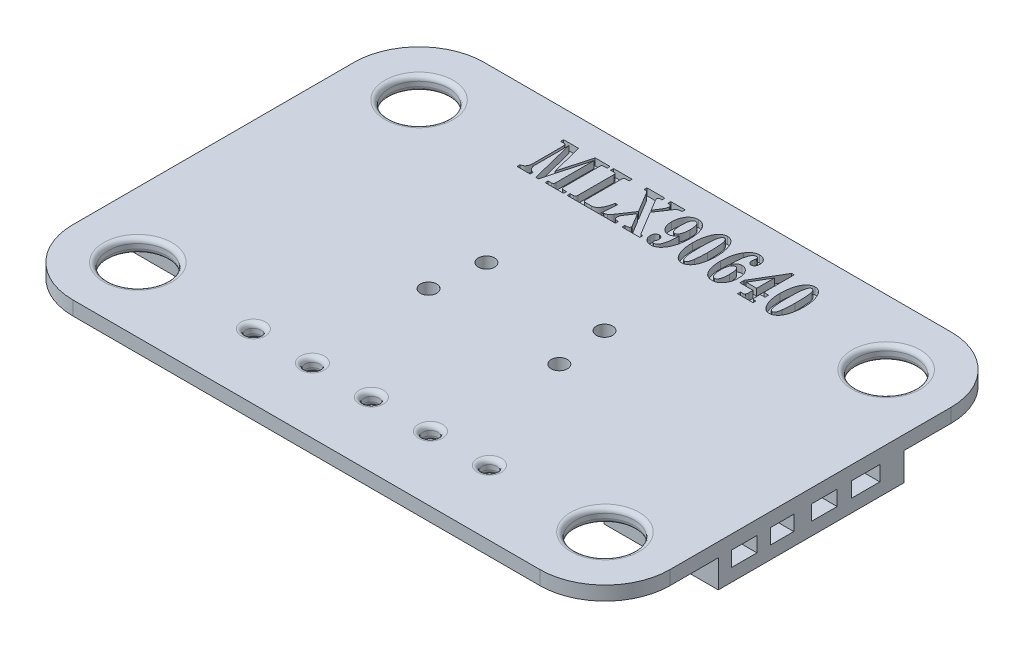
SolidWorks part; units mm, degrees
ref_plane "Alzado" through (0, 0, 0) normal (0, 0, 1) x (1, 0, 0)
ref_plane "Planta" through (0, 0, 0) normal (0, 1, 0) x (1, 0, 0)
ref_plane "Vista lateral" through (0, 0, 0) normal (1, 0, 0) x (0, 0, -1)
sketch "Croquis2" plane through (0, 0, 0) normal (0, 1, 0) x (1, 0, 0)
  line L1 (-10.05, 8.85) -> (10.05, 8.85)
  line L2 (-12.85, 6.05) -> (-12.85, -6.05)
  line L3 (-10.05, -8.85) -> (10.05, -8.85)
  line L4 (12.85, 6.05) -> (12.85, -6.05)
  line L5 (-12.85, 8.85) -> (12.85, -8.85) construction
  line L6 (-12.85, -8.85) -> (12.85, 8.85) construction
  arc A0 (10.05, -8.85) -> (12.85, -6.05) centre (10.05, -6.05) ccw
  arc A1 (-12.85, -6.05) -> (-10.05, -8.85) centre (-10.05, -6.05) ccw
  arc A2 (10.05, 8.85) -> (12.85, 6.05) centre (10.05, 6.05) cw
  arc A3 (-10.05, 8.85) -> (-12.85, 6.05) centre (-10.05, 6.05) ccw
  point P0 (0, 0)
  dimension "D3" = 2.8
  dimension "D1" = 17.7
  dimension "D2" = 25.7
extrude "Saliente-Extruir1" add sketch "Croquis2" along normal blind 0.6
sketch "Croquis3" plane through (0, 0.6, 0) normal (0, 1, 0) x (1, 0, 0)
  line L0 (-10.05, -6.05) -> (-5.08, -6.05) construction
  line L1 (-5.08, -6.05) -> (-2.54, -6.05) construction
  line L2 (-2.54, -6.05) -> (0, -6.05) construction
  line L3 (0, -6.05) -> (2.54, -6.05) construction
  line L4 (5.08, -6.05) -> (10.05, -6.05) construction
  line L5 (2.19, 1.4404) -> (-2.19, 1.4404) construction
  line L6 (2.54, -6.05) -> (5.08, -6.05) construction
  line L7 (2.2166, 1.3065) -> (-2.8146, -0.7775) construction
  line L8 (-3.1379, -0.9115) -> (-6.0577, -2.1209) construction
  circle A0 centre (-10.05, 6.05) radius 1.27
  circle A1 centre (10.05, 6.05) radius 1.27
  circle A2 centre (10.05, -6.05) radius 1.27
  circle A3 centre (-10.05, -6.05) radius 1.27
  circle A4 centre (-5.08, -6.05) radius 0.32
  circle A5 centre (-2.54, -6.05) radius 0.32
  circle A6 centre (0, -6.05) radius 0.32
  circle A7 centre (2.54, -6.05) radius 0.32
  circle A8 centre (5.08, -6.05) radius 0.32
  arc A9 (-2.6941, 1.1262) -> (-2.8874, -0.4352) centre (0, 0) ccw
  circle A10 centre (-2.54, 1.4404) radius 0.35
  circle A12 centre (2.54, 1.4404) radius 0.35
  circle A14 centre (-2.8146, -0.7775) radius 0.35
  circle A15 centre (2.8146, -0.7775) radius 0.35
  arc A16 (-2.7013, -1.1087) -> (2.7013, -1.1087) centre (0, 0) ccw
  arc A17 (2.8874, -0.4352) -> (2.6941, 1.1262) centre (0, 0) ccw
  arc A18 (2.3494, 1.734) -> (-2.3494, 1.734) centre (0, 0) ccw
  point P35 (0, 0)
  dimension "D1" = 2.54
  dimension "D2" = 0.64
  dimension "D3" = 5.84
  dimension "D6" = 0.7
  dimension "4.4" = 4.97
  dimension "D4" = 2.54
  dimension "D5" = 22.5
extrude "Cortar-Extruir1" cut sketch "Croquis3" against normal through all contours A10 | A14 | A12 | A15 | A1 | A0 | A3 | A2 | A4 | A5 | A6 | A7 | A8 region at (-10.05, 0.6, -6.05) region at (10.05, 0.6, -6.05) region at (10.05, 0.6, 6.05) region at (-10.05, 0.6, 6.05) region at (-5.08, 0.6, 6.05) region at (-2.54, 0.6, 6.05) region at (0, 0.6, 6.05) region at (2.54, 0.6, 6.05) region at (5.08, 0.6, 6.05) region at (-2.54, 0.6, -1.4404) region at (-2.8146, 0.6, 0.7775) region at (2.54, 0.6, -1.4404) region at (2.8146, 0.6, 0.7775)
fillet "Redondeo1" radius 0.2 8 edges at (-10.05, 0.6, 7.32) (-10.05, 0, 7.32) (10.05, 0.6, 7.32) (10.05, 0, 7.32) (10.05, 0.6, -4.78) (10.05, 0, -4.78) (-10.05, 0.6, -4.78) (-10.05, 0, -4.78)
fillet "Redondeo2" radius 0.2 10 edges at (5.08, 0.6, 6.37) (5.08, 0, 6.37) (2.54, 0.6, 6.37) (2.54, 0, 6.37) (0, 0.6, 6.37) (0, 0, 6.37) (-2.54, 0.6, 6.37) (-2.54, 0, 6.37) (-5.08, 0.6, 6.37) (-5.08, 0, 6.37)
sketch "Croquis4" plane through (0, 0.6, 0) normal (0, 1, 0) x (1, 0, 0)
  text T0 "MLX90640" font "Century Schoolbook" height 2
extrude "Cortar-Extruir2" cut sketch "Croquis4" against normal blind 0.3
sketch "Croquis5" plane through (0, 0, 0) normal (0, -1, 0) x (1, 0, 0)
  line L0 (-10.05, 6.05) -> (-10.05, -6.05) construction
  line L1 (0, 0) -> (0, 9.8011) construction
  line L2 (0, 9.8011) -> (0, -9.1948) construction
  line L3 (-12.85, 3.972) -> (-7.9217, 3.972)
  line L4 (-12.85, -6.05) -> (-12.85, 6.05) construction
  line L5 (-7.9217, 3.972) -> (-7.9217, -4.028)
  line L6 (-7.9217, -4.028) -> (-12.85, -4.028)
  line L7 (-12.85, -4.028) -> (-12.85, 3.972)
  line L8 (-7.1133, 1.5566) -> (-7.1133, -0.378) construction
  line L9 (-7.1133, -0.378) -> (-7.1133, -0.828) construction
  line L10 (-7.1133, -0.828) -> (-7.1133, -1.278) construction
  line L11 (-7.1133, -1.278) -> (-7.1133, -1.728) construction
  line L12 (-7.1133, -2.178) -> (-7.1133, -4.028) construction
  line L13 (-7.1133, -1.728) -> (-7.1133, -2.178) construction
  line L14 (-12.85, 3.972) -> (-12.85, 3.052) construction
  line L15 (-7.1133, -0.378) -> (-7.9217, -0.378)
  line L16 (-7.1133, -0.378) -> (-7.1133, -0.4573)
  line L17 (-7.1133, -0.4573) -> (-7.9217, -0.4573)
  line L18 (-7.9217, -0.378) -> (-7.9217, -0.4573)
  line L19 (-7.1133, -0.828) -> (-7.9217, -0.828)
  line L20 (-7.1133, -0.828) -> (-7.1133, -0.9002)
  line L21 (-7.1133, -0.9002) -> (-7.9217, -0.9002)
  line L22 (-7.9217, -0.828) -> (-7.9217, -0.9002)
  line L23 (-7.1133, -1.278) -> (-7.9217, -1.278)
  line L24 (-7.1133, -1.278) -> (-7.1133, -1.3571)
  line L25 (-7.1133, -1.3571) -> (-7.9217, -1.3571)
  line L26 (-7.9217, -1.278) -> (-7.9217, -1.3571)
  line L27 (-7.1133, -1.728) -> (-7.9217, -1.728)
  line L28 (-7.1133, -1.728) -> (-7.1133, -1.8182)
  line L29 (-7.1133, -1.8182) -> (-7.9217, -1.8182)
  line L30 (-7.9217, -1.728) -> (-7.9217, -1.8182)
  line L31 (-12.85, 3.052) -> (-12.85, 1.512) construction
  line L32 (-12.85, 1.512) -> (-12.85, -0.028) construction
  line L33 (-12.85, -0.028) -> (-12.85, -1.568) construction
  line L34 (-12.85, -1.568) -> (-12.85, -3.108) construction
  line L35 (-12.85, -3.108) -> (-12.85, -4.028)
  line L36 (-12.85, -3.108) -> (-12.85, -1.4852)
  line L37 (-12.85, -1.4852) -> (-12.85, -4.028)
  line L38 (-12.85, -4.028) -> (-2.2144, -4.028) construction
  line L39 (7.1133, -1.8182) -> (7.9217, -1.8182)
  line L40 (7.9217, -1.728) -> (7.9217, -1.8182)
  line L41 (7.1133, -1.728) -> (7.9217, -1.728)
  line L42 (7.1133, -1.728) -> (7.1133, -1.8182)
  line L43 (7.1133, -1.3571) -> (7.9217, -1.3571)
  line L44 (7.9217, -1.278) -> (7.9217, -1.3571)
  line L45 (7.1133, -1.278) -> (7.9217, -1.278)
  line L46 (7.1133, -1.278) -> (7.1133, -1.3571)
  line L47 (7.1133, -0.9002) -> (7.9217, -0.9002)
  line L48 (7.9217, -0.828) -> (7.9217, -0.9002)
  line L49 (7.1133, -0.828) -> (7.9217, -0.828)
  line L50 (7.1133, -0.828) -> (7.1133, -0.9002)
  line L51 (7.1133, -0.4573) -> (7.9217, -0.4573)
  line L52 (7.9217, -0.378) -> (7.9217, -0.4573)
  line L53 (7.1133, -0.378) -> (7.9217, -0.378)
  line L54 (7.1133, -0.378) -> (7.1133, -0.4573)
  line L55 (7.9217, -4.028) -> (12.85, -4.028)
  line L56 (7.9217, 3.972) -> (7.9217, -4.028)
  line L57 (12.85, 3.972) -> (7.9217, 3.972)
  line L58 (12.85, -4.028) -> (12.85, 3.972)
  point P57 (12.85, -3.108)
  point P58 (12.85, -1.568)
  point P59 (12.85, -0.028)
  point P60 (12.85, 1.512)
  point P61 (12.85, 3.052)
  line M44 (-12.85, 6.05) -> (-12.85, -6.05)
  line M48 (12.85, -6.05) -> (12.85, 6.05)
  dimension "D1" = 0.45
  dimension "D2" = 1.85
  dimension "D3" = 1.54
  dimension "D4" = 1.54
  dimension "D5" = 1.54
  dimension "D6" = 8
  dimension "D7" = 1.54
extrude "Saliente-Extruir4" add sketch "Croquis5" along normal blind 1.2 contours L6 L5 L3 L7 M44 | L17 L16 L15 L5 | L25 L24 L23 L5 | L21 L20 L19 L5 | L29 L28 L27 L5 | L57 L56 L52 L48 L44 L40 L55 M48 | L53 L54 L51 L52 | L49 L50 L47 L48 | L45 L46 L43 L44 | L41 L42 L39 L40 | L21 L22 L19 L20 | L45 L44 L43 L46 | L41 L40 L39 L42 region at (-10.3858, 0, -0.028) region at (-7.5175, 0, -0.4176) region at (-7.5175, 0, -0.8641) region at (-7.5175, 0, -1.7731) region at (-7.5175, 0, -1.3175) region at (7.5175, 0, -1.7731) region at (10.3858, 0, -0.028) region at (7.5175, 0, -1.3175) region at (7.5175, 0, -0.8641) region at (7.5175, 0, -0.4176)
fillet "Redondeo3" radius 0.01 24 edges at (-7.5175, 0, -1.8182) (-7.5175, 0, -1.728) (-7.5175, 0, -1.3571) (-7.5175, 0, -1.278) (-7.5175, 0, -0.9002) (-7.5175, 0, -0.828) (-7.5175, 0, -0.4573) (-7.5175, 0, -0.378) (-7.1133, -0.6, -1.8182) (-7.1133, -1.2, -1.7731) (-7.1133, -0.6, -1.728) (-7.1133, 0, -1.7731) (-7.1133, -0.6, -1.3571) (-7.1133, -1.2, -1.3175) (-7.1133, -0.6, -1.278) (-7.1133, 0, -1.3175) (-7.1133, -0.6, -0.9002) (-7.1133, -1.2, -0.8641) (-7.1133, -0.6, -0.828) (-7.1133, 0, -0.8641) (-7.1133, -0.6, -0.4573) (-7.1133, -1.2, -0.4176) (-7.1133, -0.6, -0.378) (-7.1133, 0, -0.4176)
sketch "Croquis7" plane through (0, 0, -1.8182) normal (0, 0, -1) x (-1, 0, 0)
  line L1 (7.1233, -0.01) -> (7.1233, -1.2) construction
  line L2 (7.1233, -0.2153) -> (7.9217, -0.2153)
  line L3 (7.9217, -1.2) -> (7.9217, -0.01) construction
  line L4 (7.9217, -0.2153) -> (7.9217, -1.2)
  line L5 (7.9217, -1.2) -> (7.1233, -1.2)
  line L7 (7.1233, -0.2153) -> (6.9602, -0.2153)
  line L8 (6.9602, -0.2153) -> (6.9602, -1.2)
  line L9 (6.9602, -1.2) -> (7.9217, -1.2)
  line M1 (7.9217, -1.2) -> (7.9217, -0.01)
  line M3 (7.1233, -0.01) -> (7.1233, -1.2)
  line M4 (7.1233, -1.2) -> (7.9217, -1.2)
extrude "Cortar-Extruir4" cut sketch "Croquis7" against normal blind 2.2 contours L2 M3 M4 M1 | L8 L9 L7 M3 region at (-7.0418, -0.7076, -1.8182) region at (-7.5225, -0.7076, -1.8182)
ref_plane "Plano1" through (0, 0, 0) normal (1, 0, 0) x (0, 0, -1)
mirror "Simetría1" about plane through (0, 0, 0) normal (1, 0, 0) of "Saliente-Extruir4", "Cortar-Extruir4"
sketch "Croquis8" plane through (-12.85, 0, 0) normal (-1, 0, 0) x (0, 0, 1)
  line L0 (-4.028, 0) -> (3.972, 0) construction
  line L1 (3.972, 0) -> (3.972, -1.1768) construction
  line L2 (3.972, -1.1768) -> (-4.028, -1.1768) construction
  line L3 (-4.028, -1.2) -> (-4.028, 0) construction
  line L4 (-2.9784, 0) -> (-2.9784, -0.6479)
  line L5 (-2.9784, -0.6479) -> (-1.7536, -0.6479)
  line L6 (-1.7536, -0.6479) -> (-1.7536, 0)
  line L7 (-1.7536, 0) -> (-2.9784, 0)
  line L8 (-1.1413, 0) -> (-1.1413, -0.6479)
  line L9 (-1.1413, -0.6479) -> (-0.028, -0.6479)
  line L10 (-0.028, -0.6479) -> (-0.028, 0)
  line L11 (-0.028, 0) -> (-1.1413, 0)
  line L12 (0.7237, 0) -> (0.7237, -0.6479)
  line L13 (0.7237, -0.6479) -> (1.6423, -0.6479)
  line L14 (1.6423, -0.6479) -> (1.737, -0.6479)
  line L15 (1.9485, 0) -> (0.7237, 0)
  line L16 (2.5052, 0) -> (2.5052, -0.6479)
  line L17 (2.5052, -0.6479) -> (3.3959, -0.6479)
  line L18 (3.3959, -0.6479) -> (3.3959, 0)
  line L19 (3.3959, 0) -> (2.3104, 0)
  line L20 (2.3104, 0) -> (2.3104, -0.6479)
  line L21 (2.3104, -0.6479) -> (2.5052, -0.6479)
  line L22 (1.737, -0.6479) -> (1.737, 0)
  line L23 (1.737, 0) -> (0.7237, 0)
extrude "Cortar-Extruir5" cut sketch "Croquis8" against normal blind 2.2 contours L6 L7 L4 L5 | L10 L11 L8 L9 | L14 L22 L15 L12 L13 | L18 L19 L16 L17 | L17 L18 L19 L20 L21 region at (-12.85, -0.324, -2.366) region at (-12.85, -0.324, -0.5846) region at (-12.85, -0.324, 1.2303) region at (-12.85, -0.324, 2.9506)
mirror "Simetría2" about plane through (0, 0, 0) normal (1, 0, 0) of "Cortar-Extruir5"
sketch "Croquis9" plane through (0, 0, 0) normal (0, -1, 0) x (-1, 0, 0)
  line L1 (-4.9107, 1.964) -> (-6.0434, 1.964)
  line L2 (-4.9107, 1.964) -> (-4.9107, 0)
  line L3 (-4.9107, 0) -> (-6.0434, 0)
  line L4 (-6.0434, 1.964) -> (-6.0434, 0)
  line L5 (-4.9107, 1.964) -> (-6.0434, 0) construction
  line L6 (-4.9107, 0) -> (-6.0434, 1.964) construction
  line L7 (-4.3444, -2.6791) -> (-5.4771, -2.6791)
  line L8 (-4.3444, -2.6791) -> (-4.3444, -3.3406)
  line L9 (-4.3444, -3.3406) -> (-5.4771, -3.3406)
  line L10 (-5.4771, -2.6791) -> (-5.4771, -3.3406)
  line L11 (-4.3444, -2.6791) -> (-5.4771, -3.3406) construction
  line L12 (-4.3444, -3.3406) -> (-5.4771, -2.6791) construction
  line L13 (-4.9107, 2.9872) -> (-6.0434, 2.9872)
  line L14 (-4.9107, 2.9872) -> (-4.9107, 3.7451)
  line L15 (-4.9107, 3.7451) -> (-6.0434, 3.7451)
  line L16 (-6.0434, 2.9872) -> (-6.0434, 3.7451)
  line L17 (-4.9107, 2.9872) -> (-6.0434, 3.7451) construction
  line L18 (-4.9107, 3.7451) -> (-6.0434, 2.9872) construction
  line L19 (5.6037, 3.6706) -> (4.8625, 3.6706)
  line L20 (5.6037, 3.6706) -> (5.6037, 2.3039)
  line L21 (5.6037, 2.3039) -> (4.8625, 2.3039)
  line L22 (4.8625, 3.6706) -> (4.8625, 2.3039)
  line L23 (5.6037, 3.6706) -> (4.8625, 2.3039) construction
  line L24 (5.6037, 2.3039) -> (4.8625, 3.6706) construction
  line L25 (6.9207, -2.0177) -> (4.2868, -2.0177)
  line L26 (6.9207, -2.0177) -> (6.9207, -3.3406)
  line L27 (6.9207, -3.3406) -> (4.2868, -3.3406)
  line L28 (4.2868, -2.0177) -> (4.2868, -3.3406)
  line L29 (6.9207, -2.0177) -> (4.2868, -3.3406) construction
  line L30 (6.9207, -3.3406) -> (4.2868, -2.0177) construction
  line L31 (0.6745, 0.4792) -> (-0.6745, 0.4792)
  line L32 (0.6745, 0.4792) -> (0.6745, -0.4792)
  line L33 (0.6745, -0.4792) -> (-0.6745, -0.4792)
  line L34 (-0.6745, 0.4792) -> (-0.6745, -0.4792)
  line L35 (0.6745, 0.4792) -> (-0.6745, -0.4792) construction
  line L36 (0.6745, -0.4792) -> (-0.6745, 0.4792) construction
  line L37 (7.8081, -4.6863) -> (7.0931, -4.6863)
  line L38 (7.8081, -4.6863) -> (7.8081, -5.6444)
  line L39 (7.8081, -5.6444) -> (7.0931, -5.6444)
  line L40 (7.0931, -4.6863) -> (7.0931, -5.6444)
  line L41 (7.8081, -4.6863) -> (7.0931, -5.6444) construction
  line L42 (7.8081, -5.6444) -> (7.0931, -4.6863) construction
  line L43 (8.9275, -4.2417) -> (8.4677, -4.2417)
  line L44 (8.9275, -4.2417) -> (8.9275, -4.5003)
  line L45 (8.9275, -4.5003) -> (8.4677, -4.5003)
  line L46 (8.4677, -4.2417) -> (8.4677, -4.5003)
  line L47 (8.9275, -4.2417) -> (8.4677, -4.5003) construction
  line L48 (8.9275, -4.5003) -> (8.4677, -4.2417) construction
  point P0 (-5.4771, 0.982)
  point P5 (-4.9107, -3.0099)
  point P10 (-5.4771, 3.3662)
  point P15 (5.2331, 2.9872)
  point P20 (5.6037, -2.6791)
  point P25 (0, 0)
  point P31 (7.4506, -5.1654)
  point P36 (8.6976, -4.371)
extrude "Saliente-Extruir5" add sketch "Croquis9" along normal blind 0.5
sketch "Croquis11" plane through (0, 0, -1.8182) normal (0, 0, -1) x (-1, 0, 0)
  line L0 (7.9217, -0.01) -> (7.9217, -0.25)
  line L1 (7.9217, -1.2) -> (7.9217, -0.01) construction
  line L2 (7.9217, -0.25) -> (7.002, -0.25)
  line L4 (-10.05, 0) -> (10.05, 0) construction
  line L5 (7.002, 0) -> (7.9217, -0.01)
  line L6 (7.9217, -1.2) -> (7.1133, -1.2)
  line L8 (7.1133, -1.2) -> (7.1133, -0.0019) construction
  line L9 (7.1133, -0.25) -> (7.9217, -0.25)
  line L10 (7.9217, -0.25) -> (7.9217, -1.2)
  line L11 (7.1133, -1.2) -> (7.002, -1.2)
  line L12 (7.002, -1.2) -> (7.002, -0.25)
  line M3 (7.1133, -0.0019) -> (7.1133, -1.2)
  line M4 (7.1133, -1.2) -> (7.9217, -1.2)
  line M5 (7.9217, -1.2) -> (7.9217, -0.01)
extrude "Cortar-Extruir7" cut sketch "Croquis11" against normal through all contours L2 M5 M3 M4 region at (-7.5175, -0.725, -1.8182)
